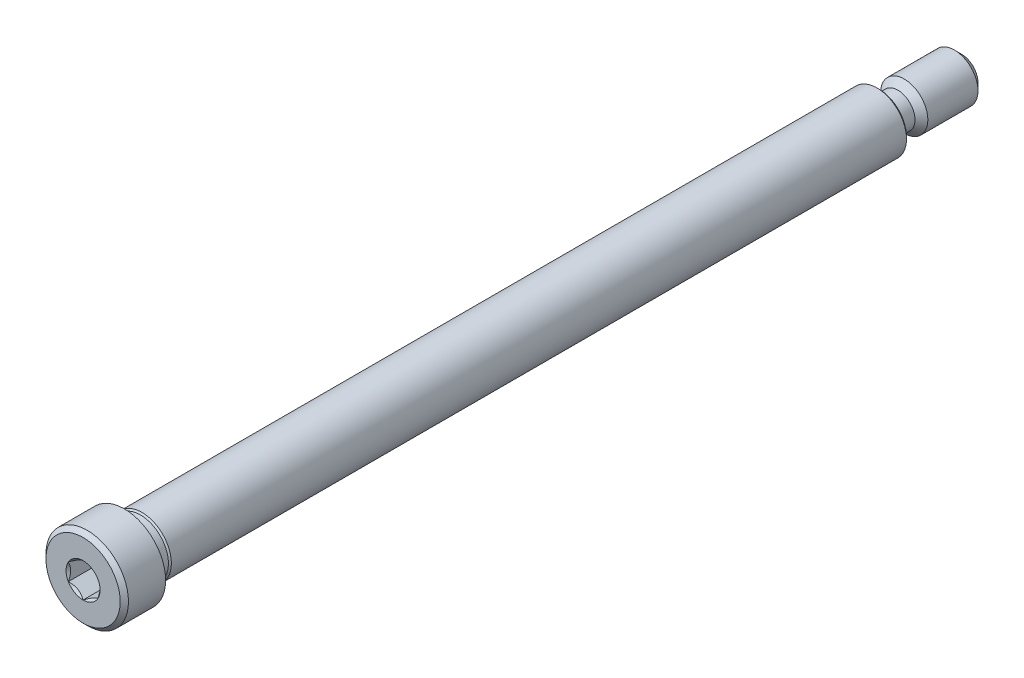
SolidWorks part; units mm, degrees
material "Alloy Steel (SS)"
ref_plane "Front Plane" through (0, 0, 0) normal (0, 0, 1) x (1, 0, 0)
ref_plane "Top Plane" through (0, 0, 0) normal (0, 1, 0) x (1, 0, 0)
ref_plane "Right Plane" through (0, 0, 0) normal (1, 0, 0) x (0, 0, -1)
sketch "Sketch2" plane through (0, 0, 0) normal (1, 0, 0) x (0, 0, -1)
  line L0 (-59.1344, 0) -> (59.1344, 0) construction
  line L1 (-59.1344, 0) -> (-59.1344, 5.5563)
  line L2 (-59.1344, 5.5563) -> (-53.5781, 5.5563)
  line L3 (-53.5781, 5.5563) -> (-53.5781, 3.9688)
  line L4 (-53.5781, 3.9688) -> (48.0219, 3.9688)
  line L5 (48.0219, 3.175) -> (59.1344, 3.175)
  line L6 (59.1344, 3.175) -> (59.1344, 0)
  line L7 (59.055, 3.3125) -> (59.69, 2.2126) construction
  line L8 (59.69, 2.2126) -> (60.325, 3.3125) construction
  line L9 (60.325, 3.3125) -> (59.055, 3.3125) construction
  line L10 (59.1344, 3.175) -> (60.2456, 3.175) construction
  line L11 (59.69, 3.3125) -> (59.69, 3.175) construction
  line L12 (59.69, 3.175) -> (59.69, 2.3501) construction
  line L13 (59.69, 2.3501) -> (59.69, 2.2126) construction
  line L14 (59.6106, 2.3501) -> (59.7694, 2.3501)
  line L15 (59.0947, 3.2437) -> (60.2853, 3.2437)
  line L16 (59.7694, 2.3501) -> (60.2853, 3.2437)
  line L17 (59.6106, 2.3501) -> (59.0947, 3.2437)
  line L18 (59.1344, 0) -> (59.1344, -3.175) construction
  line L19 (48.0219, -3.9688) -> (48.0219, 0) construction
  line L20 (48.0219, 0) -> (48.0219, 3.9688) construction
  line L21 (-59.1344, 0) -> (-59.1344, -5.5563) construction
  point P11 (-51.2159, 3.9688)
  point P12 (55.9594, -3.175)
  point P22 (59.69, 3.2437)
  point P23 (47.4663, 0)
  point P25 (-47.4663, 0)
  point P26 (-53.5781, -5.5563)
  point P29 (48.0219, -3.9688)
  dimension "Head Height" = 5.5562
  dimension "Shoulder Diameter" = 7.9375
  dimension "Screw Size Decimal Equivalent" = 6.35
  dimension "Thread Length" = 11.1125
  dimension "Head Diameter" = 11.1125
  dimension "Undercut Length" = 2.3622
  dimension "Pitch" = 1.27
  dimension "D2" = 0.1588
  dimension "D1" = 3.175
  dimension "D3" = 11.6681
  dimension "D4" = 11.6681
  dimension "Shoulder Length" = 101.6
sketch "Sketch3" plane through (0, 0, 0) normal (0, 0, 1) x (1, 0, 0)
  line L1 (0, 2.2914) -> (-1.9844, 1.1457)
  line L2 (-1.9844, 1.1457) -> (-1.9844, -1.1457)
  line L3 (-1.9844, -1.1457) -> (0, -2.2914)
  line L4 (0, -2.2914) -> (1.9844, -1.1457)
  line L5 (1.9844, -1.1457) -> (1.9844, 1.1457)
  line L6 (1.9844, 1.1457) -> (0, 2.2914)
  circle A0 centre (0, 0) radius 1.9844 construction
  dimension "Drive Size" = 3.9688
sketch "Sketch4" plane through (0, 0, 0) normal (1, 0, 0) x (0, 0, -1)
  line L0 (-53.5781, 5.5563) -> (-58.5787, 5.5562)
  line L1 (-58.5787, 5.5562) -> (-59.1344, 5.0006)
  line L2 (-53.5781, 5.5563) -> (-53.5781, 3.9688)
  line L3 (-53.5781, 3.9688) -> (-53.3797, 3.7703)
  line L4 (-53.3797, 3.7703) -> (-51.4144, 3.7703)
  line L5 (-51.4144, 3.7703) -> (-51.2159, 3.9688)
  line L6 (-53.5781, 3.9688) -> (48.0219, 3.9688) construction
  line L7 (-59.1344, 0) -> (59.1344, 0) construction
  line L8 (-51.2159, 3.9688) -> (47.7573, 3.9688)
  line L9 (47.7573, 3.9688) -> (48.0219, 3.7042)
  line L10 (48.0219, 3.7042) -> (48.0219, 0)
  line L11 (48.0219, 3.9688) -> (48.0219, 3.7042) construction
  line L12 (48.0219, 3.7042) -> (48.0219, 3.4396) construction
  line L13 (48.0219, 3.4396) -> (48.0219, 3.175) construction
  line L14 (-59.1344, 5.0006) -> (-59.1344, 0)
  line L15 (-59.1344, 5.5563) -> (-53.5781, 5.5563) construction
  line L16 (-59.1344, 0) -> (48.0219, 0)
  dimension "D1" = 45
  dimension "D2" = 7.5406
  dimension "D3" = 45
  dimension "D4" = 45
  dimension "D5" = 10.0012
revolve "Revolve1" add sketch "Sketch4" angle 360 about L16
sketch "Sketch5" plane through (0, 0, 59.1344) normal (0, 0, 1) x (1, 0, 0)
  line L0 (1.9844, 1.1457) -> (0, 2.2914) construction
  line L1 (1.9844, -1.1457) -> (1.9844, 1.1457) construction
  line L2 (0, -2.2914) -> (1.9844, -1.1457) construction
  line L3 (-1.9844, -1.1457) -> (0, -2.2914) construction
  line L4 (-1.9844, 1.1457) -> (-1.9844, -1.1457) construction
  line L5 (0, 2.2914) -> (-1.9844, 1.1457) construction
  line L6 (1.9844, 1.1457) -> (0, 2.2914)
  line L7 (1.9844, -1.1457) -> (1.9844, 1.1457)
  line L8 (0, -2.2914) -> (1.9844, -1.1457)
  line L9 (-1.9844, -1.1457) -> (0, -2.2914)
  line L10 (-1.9844, 1.1457) -> (-1.9844, -1.1457)
  line L11 (0, 2.2914) -> (-1.9844, 1.1457)
extrude "Cut-Extrude1" cut sketch "Sketch5" against normal blind 4.1672
sketch "Sketch6" plane through (0, 0, 59.1344) normal (0, 0, 1) x (1, 0, 0)
  circle A0 centre (0, 0) radius 2.2914
extrude "Cut-Extrude4" cut sketch "Sketch6" against normal blind 4.1672 draft 45
sketch "Sketch7" plane through (0, 0, 0) normal (1, 0, 0) x (0, 0, -1)
  line L0 (48.0219, 3.175) -> (58.1819, 3.175)
  line L1 (48.0219, 3.175) -> (59.1344, 3.175) construction
  line L2 (58.1819, 3.175) -> (59.1344, 2.2225)
  line L3 (59.1344, 3.175) -> (59.1344, 0) construction
  line L4 (59.1344, 2.2225) -> (59.1344, 0)
  line L5 (59.1344, 0) -> (48.0219, 0)
  line L6 (48.0219, -3.7042) -> (48.0219, 3.7042) construction
  line L7 (48.0219, 0) -> (48.0219, 3.175)
  dimension "D1" = 45
  dimension "D2" = 0.9525
revolve "Revolve2" add sketch "Sketch7" angle 360 about L5
sketch "Sketch10" plane through (0, 0, 0) normal (1, 0, 0) x (0, 0, -1)
  line L0 (48.8855, 2.3114) -> (50.5619, 2.3114)
  line L1 (50.5619, 2.3114) -> (52.2192, 3.9688)
  line L2 (52.2192, 3.9688) -> (48.0219, 3.9688)
  line L3 (48.0219, 3.9688) -> (48.0219, 3.175)
  line L4 (48.0219, -3.7042) -> (48.0219, 3.7042) construction
  line L5 (59.1344, 0) -> (48.0219, 0) construction
  line L6 (-59.1344, 0) -> (59.1344, 0) construction
  arc A0 (48.0219, 3.175) -> (48.8855, 2.3114) centre (48.8855, 3.175) ccw
  dimension "Flat OD" = 4.6228
  dimension "Flat" = 2.54
  dimension "D3" = 45
revolve "Cut-Revolve1" cut sketch "Sketch10" angle 360 about L5
sketch "Sketch8" [suppressed] plane through (0, 0, -59.1344) normal (0, 0, -1) x (-1, 0, 0)
  circle A0 centre (0, 0) radius 3.175 construction
  circle A1 centre (0, 0) radius 3.175
curve "Helix/Spiral1" [suppressed] pitch 1.27 height 12.3825 turns 9.75
sketch "Sketch9" [suppressed] plane through (0, 0, 0) normal (1, 0, 0) x (0, 0, -1)
  line L0 (59.6106, 2.3501) -> (59.7694, 2.3501) construction
  line L1 (59.7694, 2.3501) -> (60.2853, 3.2437) construction
  line L2 (59.0947, 3.2437) -> (60.2853, 3.2437) construction
  line L3 (59.6106, 2.3501) -> (59.0947, 3.2437) construction
  line L4 (59.6106, 2.3501) -> (59.7694, 2.3501)
  line L5 (59.7694, 2.3501) -> (60.2853, 3.2437)
  line L6 (59.0947, 3.2437) -> (60.2853, 3.2437)
  line L7 (59.6106, 2.3501) -> (59.0947, 3.2437)
ref_plane "Plane1" [suppressed] through (0, 0, -50.5619) normal (0, 0, 1) x (1, 0, 0)
split "Split1" [suppressed] bodies to split 138
sweep "Cut-Sweep1" [suppressed] cut profiles "Sketch9" path "Helix/Spiral1"
combine bodies "Combine1" [suppressed] operation type add bodies to combine 141 139
sketch "Sketch11" [suppressed] plane through (0, 0, 59.1344) normal (0, 0, 1) x (1, 0, 0)
  line L0 (-0.0802, 5.5562) -> (0.0802, 5.5562)
  line L1 (0.0802, 5.5562) -> (0, 5.4173)
  line L2 (0, 0) -> (0, 5.5563) construction
  line L3 (0, 5.4173) -> (-0.0802, 5.5562)
  line L4 (0, 0) -> (5.5562, 0) construction
  circle A0 centre (0, 0) radius 5.5562 construction
  point P6 (0, 5.5562)
  dimension "D1" = 10.8347
  dimension "D2" = 60
  dimension "D3" = 0.1604
sketch "Sketch12" [suppressed] plane through (0, 0, 0) normal (1, 0, 0) x (0, 0, -1)
  line L0 (-59.1344, 5.4173) -> (-55.3025, 5.4173)
  line L1 (-54.8283, 5.8916) -> (-54.8283, 5.5563) construction
  line L2 (-59.1344, 5.5563) -> (-53.5781, 5.5563) construction
  arc A0 (-55.3025, 5.4173) -> (-54.8283, 5.8916) centre (-55.3025, 5.8916) ccw
  point P11 (-54.9672, 5.5563)
  dimension "D1" = 1.3891
sweep "Cut-Sweep2" [suppressed] cut profiles "Sketch11" path "Sketch12"
pattern_circular "CirPattern1" [suppressed] count 76 over 360 about axis through (0, 0, 59.1344) along (0, 0, -1) of bodies 143
equation "\"D2@Sketch2\" = \"Pitch@Sketch2\" / 8"
equation "\"D1@Sketch2\"=\"Pitch@Sketch2\"*2.5"
equation "\"D2@Sketch4\"=\"Shoulder Diameter@Sketch2\"*0.95"
equation "\"D5@Sketch4\"=\"Head Diameter@Sketch2\"*0.9"
equation "\"D1@Cut-Extrude1\"=\"Head Height@Sketch2\"*0.75"
equation "\"D1@Cut-Extrude4\"=\"D1@Cut-Extrude1\""
equation "\"D2@Sketch7\"=\"pitch@sketch2\"*0.75"
equation "\"D3@Helix/Spiral1\"=\"Thread Length@Sketch2\"+\"Pitch@Sketch2\""
equation "\"D4@Helix/Spiral1\"=\"Pitch@Sketch2\""
equation "\"D1@Sketch11\"=\"Head Diameter@Sketch2\"*0.975"
equation "\"D1@Sketch12\"=\"Head Height@Sketch2\"*0.25"
equation "\"D1@CirPattern1\"=\"Head Diameter@Sketch2\" * 3.14 / \"D3@Sketch11\" * 0.35"
equation "\"D3@Sketch2\"=\"Thread Length@Sketch2\"*1.05"
equation "\"D4@Sketch2\"=\"D3@Sketch2\""
